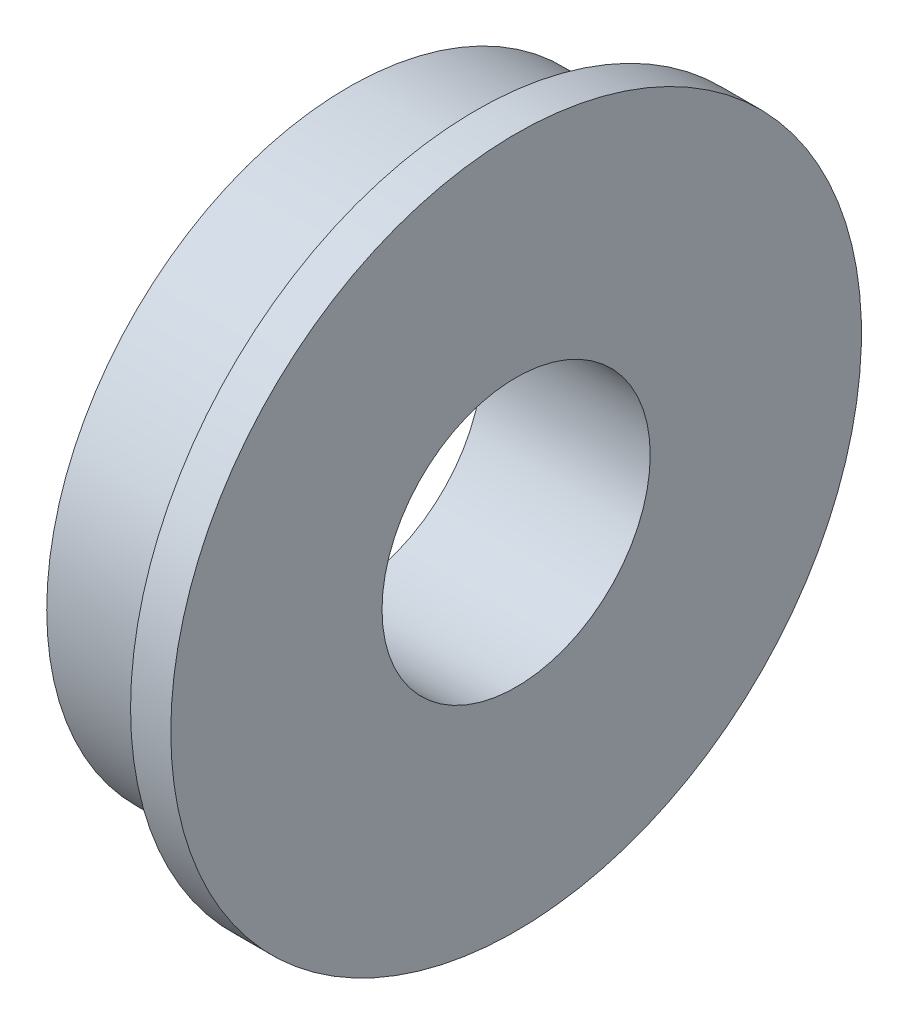
SolidWorks part; units mm, degrees
ref_plane "Plan de face" through (0, 0, 0) normal (0, 0, 1) x (1, 0, 0)
ref_plane "Plan de dessus" through (0, 0, 0) normal (0, 1, 0) x (1, 0, 0)
ref_plane "Plan de droite" through (0, 0, 0) normal (1, 0, 0) x (0, 0, -1)
sketch "Esquisse1" plane through (0, 0, 0) normal (0, 0, 1) x (1, 0, 0)
  line L0 (0, 2) -> (2.5, 2)
  line L1 (2.5, 2) -> (2.5, 5.15)
  line L2 (2.5, 5.15) -> (1.9, 5.15)
  line L3 (1.9, 5.15) -> (1.9, 4.5)
  line L4 (1.9, 4.5) -> (0, 4.5)
  line L5 (0, 4.5) -> (0, 2)
  line L6 (0, 0) -> (2.5, 0) construction
  point P2 (0, 0)
  point P10 (0, 0)
  dimension "D1" = 2
  dimension "D2" = 4.5
  dimension "D3" = 2.5
  dimension "D4" = 5.15
  dimension "D5" = 0.6
revolve "Révolution1" add sketch "Esquisse1" angle 360 about L6
